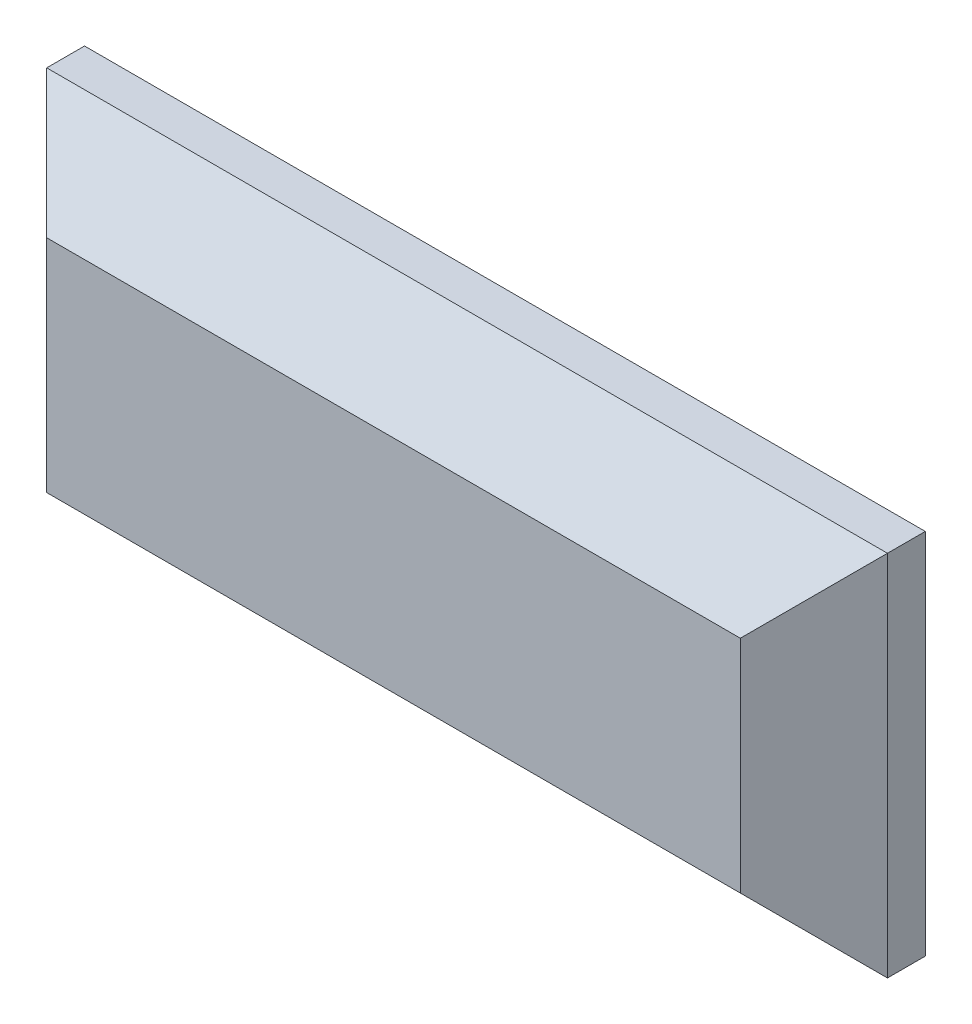
SolidWorks part; units mm, degrees
ref_plane "Спереди" through (0, 0, 0) normal (0, 0, 1) x (1, 0, 0)
ref_plane "Сверху" through (0, 0, 0) normal (0, 1, 0) x (1, 0, 0)
ref_plane "Справа" through (0, 0, 0) normal (1, 0, 0) x (0, 0, -1)
sketch "Эскиз1" plane through (0, 0, 0) normal (0, 0, 1) x (1, 0, 0)
  line L1 (-203.1392, 1392.9521) -> (-123.1392, 1392.9521)
  line L2 (-203.1392, 1392.9521) -> (-203.1392, 1357.9521)
  line L3 (-203.1392, 1357.9521) -> (-123.1392, 1357.9521)
  line L4 (-123.1392, 1392.9521) -> (-123.1392, 1357.9521)
  dimension "D1" = 80
  dimension "D2" = 35
extrude "Бобышка-Вытянуть1" add sketch "Эскиз1" along normal blind 10
sketch "Эскиз7" plane through (0, 0, 0) normal (0, 0, -1) x (-1, 0, 0)
  line L0 (163.1392, 1392.9521) -> (163.1392, 1357.9521) construction
  line L1 (140.6392, 1385.4521) -> (185.6392, 1385.4521)
  line L2 (140.6392, 1385.4521) -> (140.6392, 1365.4521)
  line L3 (140.6392, 1365.4521) -> (185.6392, 1365.4521)
  line L4 (185.6392, 1385.4521) -> (185.6392, 1365.4521)
  line L5 (123.1392, 1392.9521) -> (203.1392, 1392.9521) construction
  line L6 (203.1392, 1357.9521) -> (123.1392, 1357.9521) construction
  line L7 (123.1392, 1375.4521) -> (203.1392, 1375.4521) construction
  line L8 (123.1392, 1357.9521) -> (123.1392, 1392.9521) construction
  line L9 (203.1392, 1392.9521) -> (203.1392, 1357.9521) construction
  point P16 (163.1392, 1385.4521)
  point P17 (140.6392, 1375.4521)
  dimension "D1" = 45
  dimension "D2" = 20
extrude "Бобышка-Вытянуть3" add sketch "Эскиз7" along normal blind 5.5
sketch "Эскиз8" plane through (0, 0, -5.5) normal (0, 0, -1) x (-1, 0, 0)
  line L0 (163.1392, 1385.4521) -> (163.1392, 1365.4521) construction
  line L1 (185.6392, 1385.4521) -> (140.6392, 1385.4521) construction
  line L2 (140.6392, 1365.4521) -> (185.6392, 1365.4521) construction
  line L3 (140.6392, 1375.4521) -> (185.6392, 1375.4521) construction
  line L4 (140.6392, 1385.4521) -> (140.6392, 1365.4521) construction
  line L5 (185.6392, 1365.4521) -> (185.6392, 1385.4521) construction
  circle A0 centre (152.9164, 1375.4521) radius 5.25
  circle A1 centre (173.3621, 1375.4521) radius 5.25
  point P16 (0, 0)
  dimension "D1" = 10.5
  dimension "D2" = 10.5
extrude "Вырез-Вытянуть3" cut sketch "Эскиз8" against normal up to surface (15.5 mm away) up to face at (-163.1392, 1375.4521, 10)
sketch "Эскиз9" plane through (0, 0, 10) normal (0, 0, 1) x (1, 0, 0)
  circle A0 centre (-173.3621, 1375.4521) radius 9
  circle A1 centre (-152.9164, 1375.4521) radius 9
  circle A2 centre (-152.9164, 1375.4521) radius 5.25 construction
  circle A3 centre (-173.3621, 1375.4521) radius 5.25 construction
  dimension "D1" = 18
  dimension "D2" = 18
extrude "Вырез-Вытянуть4" cut sketch "Эскиз9" against normal blind 5
sketch "Эскиз10" plane through (0, 0, 10) normal (0, 0, 1) x (1, 0, 0)
  line L1 (-203.1392, 1392.9521) -> (-123.1392, 1392.9521)
  line L2 (-203.1392, 1392.9521) -> (-203.1392, 1357.9521)
  line L3 (-203.1392, 1357.9521) -> (-123.1392, 1357.9521)
  line L4 (-123.1392, 1392.9521) -> (-123.1392, 1357.9521)
extrude "Бобышка-Вытянуть4" add sketch "Эскиз10" along normal blind 0.6
chamfer "Фаска2" distance 7 angle 45 4 edges at (-163.1392, 1357.9521, 10.6) (-123.1392, 1375.4521, 10.6) (-163.1392, 1392.9521, 10.6) (-203.1392, 1375.4521, 10.6)
ref_plane "Плоскость4" through (-163.1392, 0, 0) normal (-1, 0, 0) x (0, 0, 1)
